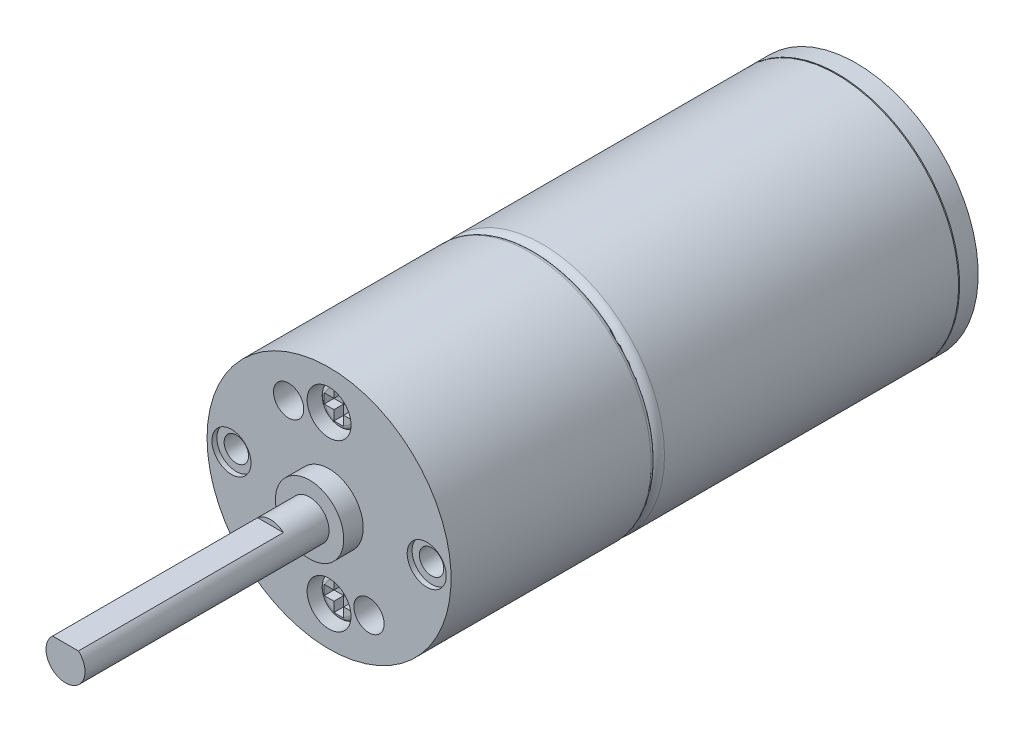
SolidWorks part; units mm, degrees
ref_plane "Alzado" through (0, 0, 0) normal (0, 0, 1) x (1, 0, 0)
ref_plane "Planta" through (0, 0, 0) normal (0, 1, 0) x (1, 0, 0)
ref_plane "Vista lateral" through (0, 0, 0) normal (1, 0, 0) x (0, 0, -1)
sketch "Croquis1" plane through (0, 0, 0) normal (0, 0, 1) x (1, 0, 0)
  circle A0 centre (0, 0) radius 12.5
extrude "Saliente-Extruir1" add sketch "Croquis1" along normal blind 21
sketch "Croquis2" plane through (0, 0, 21) normal (0, 0, 1) x (1, 0, 0)
  circle A0 centre (0, 0) radius 3.5
  dimension "D1" = 7
extrude "Saliente-Extruir2" add sketch "Croquis2" along normal blind 2
sketch "Croquis3" plane through (0, 0, 23) normal (0, 0, 1) x (1, 0, 0)
  circle A0 centre (0, 0) radius 2
extrude "Saliente-Extruir3" add sketch "Croquis3" along normal blind 25
sketch "Croquis4" plane through (0, 0, 0) normal (0, 0, -1) x (-1, 0, 0)
  circle A0 centre (0, 0) radius 12.5
fillet "Redondeo1" radius 0.5 1 edges at (12.5, 0, 0)
sketch "Croquis5" plane through (0, 0, 0) normal (0, 0, -1) x (-1, 0, 0)
  circle A0 centre (0, 0) radius 12.5
extrude "Saliente-Extruir5" add sketch "Croquis5" along normal blind 31
fillet "Redondeo2" radius 1 1 edges at (-12.5, 0, 0)
sketch "Croquis6" plane through (0, 0, 48) normal (0, 0, 1) x (1, 0, 0)
  line L0 (0, 1.5) -> (1.3229, 1.5)
  line L2 (0, 1.5) -> (-1.3229, 1.5)
  circle A1 centre (0, 0) radius 2 construction
  spline S0 degree 3 poles (-1.3229, 1.5) (-0.705, 2.1293) (0.4331, 2.3603) (1.3229, 1.5) knots 0 0 0 0 1 1 1 1
extrude "Cortar-Extruir2" cut sketch "Croquis6" against normal blind 21
sketch "Croquis7" plane through (0, 0, -31) normal (0, 0, -1) x (-1, 0, 0)
  circle A0 centre (0, 0) radius 3.2
extrude "Saliente-Extruir7" add sketch "Croquis7" along normal blind 1.5
fillet "Redondeo5" radius 0.5 1 edges at (-3.2, 0, -32.5)
sketch "Croquis10" plane through (0, 0, -32.5) normal (0, 0, -1) x (-1, 0, 0)
  circle A0 centre (0, 0) radius 3.5
  circle A1 centre (0, 0) radius 12.5
extrude "Saliente-Extruir10" add sketch "Croquis10" along normal blind 0.5 and the other way blind 1.4 separate body
sketch "Croquis11" plane through (0, 0, -33) normal (0, 0, -1) x (-1, 0, 0)
  line L1 (-7.7196, 4.7519) -> (-4.7196, 4.7519)
  line L2 (-7.7196, 4.7519) -> (-7.7196, 3.3519)
  line L3 (-7.7196, 3.3519) -> (-4.7196, 3.3519)
  line L4 (-4.7196, 4.7519) -> (-4.7196, 3.3519)
  line L5 (-7.7196, 4.7519) -> (-4.7196, 3.3519) construction
  line L6 (-7.7196, 3.3519) -> (-4.7196, 4.7519) construction
extrude "Saliente-Extruir11" add sketch "Croquis11" along normal blind 0.5
sketch "Croquis12" plane through (0, 0, -33) normal (0, 0, -1) x (-1, 0, 0)
  line L1 (6.6731, 4.1546) -> (11.1731, 4.1546)
  line L2 (6.6731, 4.1546) -> (6.6731, -0.3454)
  line L3 (6.6731, -0.3454) -> (11.1731, -0.3454)
  line L4 (11.1731, 4.1546) -> (11.1731, -0.3454)
  line L5 (6.6731, 4.1546) -> (11.1731, -0.3454) construction
  line L6 (6.6731, -0.3454) -> (11.1731, 4.1546) construction
extrude "Saliente-Extruir12" add sketch "Croquis12" along normal blind 1
fillet "Redondeo10" radius 2.25 4 edges at (-8.9231, -0.3454, -34) (-6.6731, 1.9046, -34) (-8.9231, 4.1546, -34) (-11.1731, 1.9046, -34)
sketch "Croquis15" plane through (0, 0, -33) normal (0, 0, -1) x (-1, 0, 0)
  circle A0 centre (-8.8629, -1.8618) radius 2.25
extrude "Saliente-Extruir13" add sketch "Croquis15" along normal blind 0.5
fillet "Redondeo13" radius 3.2 1 edges at (6.6129, -1.8618, -33.5)
sketch "Croquis16" plane through (0, 0, -33) normal (0, 0, -1) x (-1, 0, 0)
  line L0 (1.6742, -5.3984) -> (1.6742, -10.3984)
  line L1 (1.6742, -10.3984) -> (4.6742, -10.3984)
  line L2 (4.6742, -10.3984) -> (4.6742, -9.8984)
  line L3 (4.6742, -9.8984) -> (3.6742, -9.8984)
  line L4 (3.6742, -9.8984) -> (3.6742, -8.9824)
  line L5 (3.6742, -8.9824) -> (4.6742, -8.9824)
  line L6 (4.6742, -8.9824) -> (4.6742, -6.9824)
  line L7 (4.6742, -6.9824) -> (3.6742, -6.9824)
  line L8 (3.6742, -6.9824) -> (3.6742, -5.8984)
  line L9 (3.6742, -5.8984) -> (4.6742, -5.8984)
  line L10 (4.6742, -5.8984) -> (4.6742, -5.3984)
  line L11 (4.6742, -5.3984) -> (1.6742, -5.3984)
extrude "Saliente-Extruir14" add sketch "Croquis16" along normal blind 6
sketch "Croquis20" plane through (0, 0, -33) normal (0, 0, -1) x (-1, 0, 0)
  line L0 (1.6742, -6.9824) -> (-6.3258, -6.9824)
  line L1 (-6.3258, -6.9824) -> (-6.3258, -8.9824)
  line L2 (-6.3258, -8.9824) -> (1.6742, -8.9824)
  line L3 (4.6742, -8.9824) -> (4.6742, -6.9824) construction
  line L5 (1.6742, -8.9824) -> (1.6742, -6.9824)
  line L6 (1.6742, -5.3984) -> (1.6742, -10.3984) construction
extrude "Saliente-Extruir15" add sketch "Croquis20" along normal blind 1
sketch "Croquis21" plane through (-1.6742, 0, 0) normal (1, 0, 0) x (0, 0, -1)
  line L2 (35.5, -8.9824) -> (35, -8.9824)
  line L3 (35.5, -8.9824) -> (35.5, -9.4824)
  line L4 (35.5, -9.4824) -> (35, -9.4824)
  line L5 (35, -8.9824) -> (35, -9.4824)
extrude "Saliente-Extruir16" add sketch "Croquis21" along normal blind 6 and the other way blind 5
fillet "Redondeo16" radius 0.25 4 edges at (4.3258, -9.4824, -35.25) (4.3258, -9.2324, -35) (4.3258, -8.9824, -35.25) (4.3258, -9.2324, -35.5)
sketch "Croquis23" plane through (-1.6742, 0, 0) normal (1, 0, 0) x (0, 0, -1)
  line L1 (35.4999, -6.9899) -> (34.9999, -6.9899)
  line L2 (35.4999, -6.9899) -> (35.4999, -6.4899)
  line L3 (35.4999, -6.4899) -> (34.9999, -6.4899)
  line L4 (34.9999, -6.9899) -> (34.9999, -6.4899)
extrude "Saliente-Extruir17" add sketch "Croquis23" along normal blind 6 and the other way blind 5 contours L1 L4 L3 L2
fillet "Redondeo20" radius 0.25 4 edges at (4.3258, -6.9899, -35.2499) (4.3258, -6.7399, -34.9999) (4.3258, -6.4899, -35.2499) (4.3258, -6.7399, -35.4999)
sketch "Croquis24" plane through (0, 0, -33) normal (0, 0, -1) x (-1, 0, 0)
  line L0 (6.6742, -6.9899) -> (4.6742, -6.9899) construction
  line L1 (6.6742, -6.4899) -> (6.1742, -6.4899)
  line L2 (6.6742, -6.4899) -> (6.6742, -6.9899)
  line L3 (6.6742, -6.9899) -> (6.1742, -6.9899)
  line L4 (6.1742, -6.4899) -> (6.1742, -6.9899)
extrude "Saliente-Extruir18" add sketch "Croquis24" along normal blind 2.5
sketch "Croquis25" plane through (0, 0, -35.5) normal (0, 0, -1) x (-1, 0, 0)
  line L0 (6.6742, -9.4824) -> (3.6742, -9.4824) construction
  line L1 (6.6742, -8.9824) -> (6.1742, -8.9824)
  line L2 (6.6742, -8.9824) -> (6.6742, -9.4824)
  line L3 (6.6742, -9.4824) -> (6.1742, -9.4824)
  line L4 (6.1742, -8.9824) -> (6.1742, -9.4824)
extrude "Saliente-Extruir19" add sketch "Croquis25" along normal blind 0.0001 and the other way blind 2.5
fillet "Redondeo21" radius 0.25 1 edges at (-6.6742, -9.2324, -35.5001)
fillet "Redondeo22" radius 0.25 1 edges at (-6.6742, -6.7399, -35.5)
sketch "Croquis27" plane through (0, 0, 21) normal (0, 0, 1) x (1, 0, 0)
sketch "Croquis29" plane through (0, 0, 48) normal (0, 0, 1) x (1, 0, 0)
  line L0 (0, 0) -> (4.0885, -7.4521) construction
  line L1 (4.0885, -7.4521) -> (-4.0885, 7.4521) construction
  dimension "D1" = 8.5
  dimension "D2" = 17
sketch "Croquis30" plane through (0, 0, 21) normal (0, 0, 1) x (1, 0, 0)
  circle A0 centre (-4.1442, 7.484) radius 1.55
  circle A1 centre (4.0885, -7.4521) radius 1.55
extrude "Cortar-Extruir5" cut sketch "Croquis30" against normal blind 6
sketch "Croquis31" plane through (0, 0, 48) normal (0, 0, 1) x (1, 0, 0)
  line L0 (0, 0) -> (0, 8.5) construction
  line L1 (0, 8.5) -> (0, -8.5) construction
  dimension "D1" = 8.5
  dimension "D2" = 17
sketch "Croquis32" plane through (0, 0, 21) normal (0, 0, 1) x (1, 0, 0)
  circle A0 centre (0, -8.4713) radius 2.25
  circle A1 centre (0, 8.5) radius 2.25
  circle A2 centre (0, 8.5) radius 1.25
  circle A3 centre (0, -8.4713) radius 1.25
extrude "Cortar-Extruir7" cut sketch "Croquis32" against normal blind 3
sketch "Croquis34" plane through (0, 0, 21) normal (0, 0, 1) x (1, 0, 0)
  circle A0 centre (0, 8.5) radius 1.25
  dimension "D1" = 2.5
extrude "Cortar-Extruir8" cut sketch "Croquis34" against normal blind 18
sketch "Croquis35" plane through (0, 0, 21) normal (0, 0, 1) x (1, 0, 0)
  circle A1 centre (0, -8.4713) radius 1.25
extrude "Cortar-Extruir11" cut sketch "Croquis35" against normal blind 18
sketch "Croquis36" plane through (0, 0, 48) normal (0, 0, 1) x (1, 0, 0)
  line L0 (0, 0) -> (10, 0) construction
  line L1 (10, 0) -> (-10, 0) construction
sketch "Croquis37" plane through (0, 0, 21) normal (0, 0, 1) x (1, 0, 0)
  circle A0 centre (10.0046, 0) radius 2
  circle A1 centre (-10, 0) radius 2
extrude "Cortar-Extruir12" cut sketch "Croquis37" against normal blind 0.5
sketch "Croquis38" plane through (0, 0, 20.5) normal (0, 0, 1) x (1, 0, 0)
  circle A0 centre (-10, 0) radius 1.25
  circle A1 centre (10, 0) radius 1.25
sketch "Croquis39" plane through (0, 0, 20.5) normal (0, 0, 1) x (1, 0, 0)
  circle A0 centre (-10, 0) radius 1.25
  circle A1 centre (10, 0) radius 1.25
extrude "Cortar-Extruir14" cut sketch "Croquis39" against normal blind 6
sketch "Croquis40" plane through (0, 0, 3) normal (0, 0, 1) x (1, 0, 0)
  circle A0 centre (0, 8.5) radius 1
extrude "Saliente-Extruir20" add sketch "Croquis40" along normal blind 15
sketch "Croquis41" plane through (0, 0, 18) normal (0, 0, 1) x (1, 0, 0)
  circle A0 centre (0, 8.5) radius 2
extrude "Saliente-Extruir21" add sketch "Croquis41" along normal blind 2
sketch "Croquis42" plane through (0, 0, 21) normal (0, 0, 1) x (1, 0, 0)
  line L0 (-0.5, 9) -> (-0.5, 10)
  line L1 (-0.5, 7) -> (0.5, 7)
  line L2 (-0.5, 7) -> (-0.5, 8)
  line L3 (-0.5, 10) -> (0.5, 10)
  line L4 (0.5, 7) -> (0.5, 8)
  line L5 (-0.5, 7) -> (0.5, 10) construction
  line L6 (-0.5, 10) -> (0.5, 7) construction
  line L7 (-1.5, 8) -> (-0.5, 8)
  line L8 (-1.5, 8) -> (-1.5, 9)
  line L9 (-1.5, 9) -> (-0.5, 9)
  line L10 (1.5, 8) -> (1.5, 9)
  line L11 (-1.5, 8) -> (1.5, 9) construction
  line L12 (-1.5, 9) -> (1.5, 8) construction
  line L13 (0.5, 8) -> (1.5, 8)
  line L14 (0.5, 9) -> (0.5, 10)
  line L15 (0.5, 9) -> (1.5, 9)
  point P0 (0, 8.5)
  point P6 (0, 8.5)
extrude "Cortar-Extruir16" cut sketch "Croquis42" against normal blind 2
fillet "Redondeo27" radius 0.5 2 edges at (2, 8.5, 18) (2, 8.5, 20)
sketch "Croquis43" plane through (0, 0, 3) normal (0, 0, 1) x (1, 0, 0)
  circle A0 centre (0, -8.5) radius 1
extrude "Saliente-Extruir23" add sketch "Croquis43" along normal up to surface (15 mm away) up to face at (1.25, -8.4713, 18)
sketch "Croquis44" plane through (0, 0, 18) normal (0, 0, 1) x (1, 0, 0)
  circle A0 centre (0, -8.5) radius 2
extrude "Saliente-Extruir24" add sketch "Croquis44" along normal blind 2
sketch "Croquis45" plane through (0, 0, 20) normal (0, 0, 1) x (1, 0, 0)
  line L0 (0.5, -8) -> (1.5, -8)
  line L1 (-0.5, -10) -> (0.5, -10)
  line L2 (-0.5, -10) -> (-0.5, -9)
  line L3 (-0.5, -7) -> (0.5, -7)
  line L4 (0.5, -10) -> (0.5, -9)
  line L5 (-0.5, -10) -> (0.5, -7) construction
  line L6 (-0.5, -7) -> (0.5, -10) construction
  line L7 (-1.5, -8) -> (-0.5, -8)
  line L8 (-1.5, -8) -> (-1.5, -9)
  line L9 (-1.5, -9) -> (-0.5, -9)
  line L10 (1.5, -8) -> (1.5, -9)
  line L11 (-1.5, -8) -> (1.5, -9) construction
  line L12 (-1.5, -9) -> (1.5, -8) construction
  line L13 (-0.5, -8) -> (-0.5, -7)
  line L14 (0.5, -9) -> (1.5, -9)
  line L15 (0.5, -8) -> (0.5, -7)
  point P0 (0, -8.5)
  point P6 (0, -8.5)
extrude "Cortar-Extruir18" cut sketch "Croquis45" against normal blind 1
fillet "Redondeo32" radius 0.5 2 edges at (2, -8.5, 18) (2, -8.5, 20)
